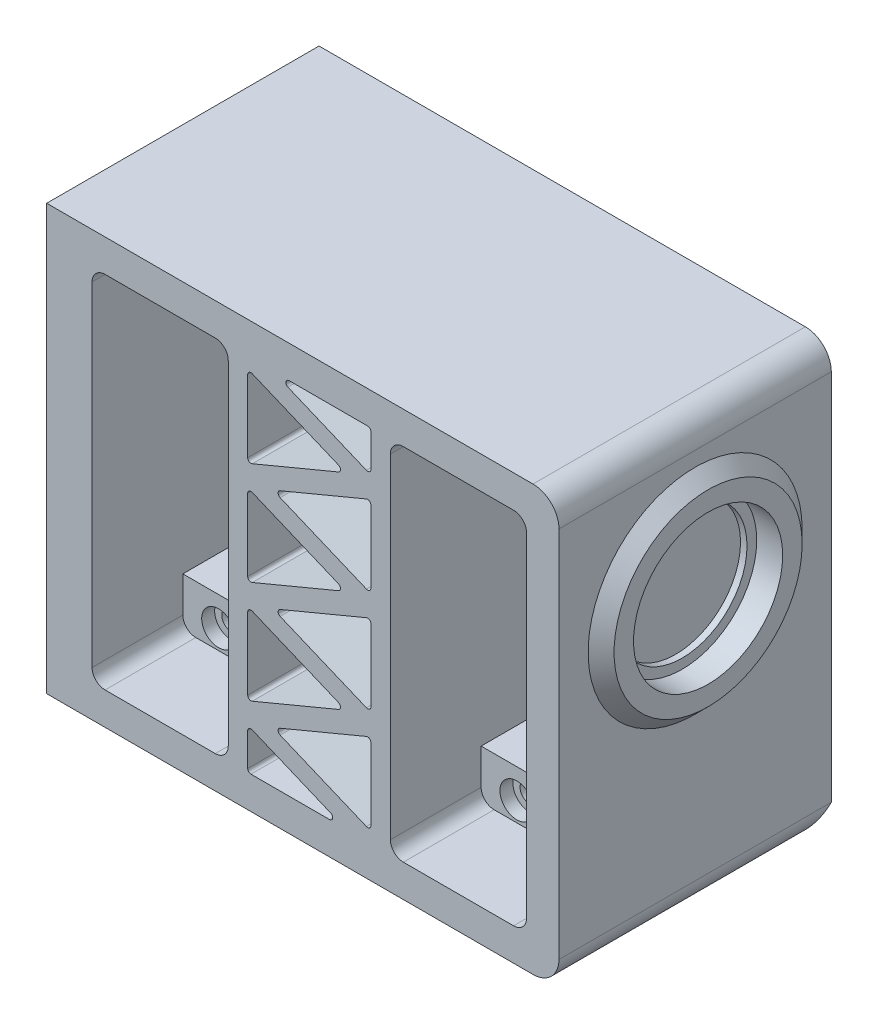
SolidWorks part; units mm, degrees
ref_plane "Front Plane" through (0, 0, 0) normal (0, 0, 1) x (1, 0, 0)
ref_plane "Top Plane" through (0, 0, 0) normal (0, 1, 0) x (1, 0, 0)
ref_plane "Right Plane" through (0, 0, 0) normal (1, 0, 0) x (0, 0, -1)
sketch "Sketch1" plane through (0, 0, 0) normal (0, 0, 1) x (1, 0, 0)
  line L0 (5, 60.5) -> (26, 60.5)
  line L1 (0, 0) -> (77, 0)
  line L2 (0, 0) -> (0, 65.5)
  line L3 (0, 65.5) -> (77, 65.5)
  line L4 (77, 0) -> (77, 65.5)
  line L5 (51, 60.5) -> (72, 60.5)
  line L6 (51, 60.5) -> (51, 5)
  line L7 (51, 5) -> (72, 5)
  line L8 (72, 60.5) -> (72, 5)
  line L9 (5, 60.5) -> (5, 5)
  line L10 (5, 5) -> (26, 5)
  line L12 (26, 60.5) -> (26, 5)
  line L13 (5, 53) -> (26, 53)
  line L14 (51, 53) -> (72, 53)
  line L15 (5, 12.5) -> (26, 12.5)
  line L16 (51, 12.5) -> (72, 12.5)
  line L17 (10.5, 57.5) -> (20.5, 57.5) construction
  line L18 (10.5, 8) -> (20.5, 8) construction
  line L19 (15.5, 57.5) -> (15.5, 8) construction
  line L20 (5, 32.75) -> (26, 32.75) construction
  line L21 (51, 32.75) -> (72, 32.75) construction
  line L22 (61.5, 57.5) -> (61.5, 8) construction
  line L23 (56.5, 57.5) -> (66.5, 57.5) construction
  line L24 (56.5, 8) -> (66.5, 8) construction
  circle A0 centre (10.5, 57.5) radius 1.5
  circle A1 centre (20.5, 57.5) radius 1.5
  circle A2 centre (10.5, 8) radius 1.5
  circle A3 centre (20.5, 8) radius 1.5
  circle A4 centre (56.5, 57.5) radius 1.5
  circle A5 centre (66.5, 57.5) radius 1.5
  circle A6 centre (66.5, 8) radius 1.5
  circle A7 centre (56.5, 8) radius 1.5
  point P33 (15.5, 32.75)
  point P34 (15.5, 32.75)
  point P41 (61.5, 32.75)
  point P42 (61.5, 32.75)
  point P53 (61.5, 8)
  point P55 (61.5, 57.5)
  dimension "D13" = 3
  dimension "D1" = 21
  dimension "D2" = 5
  dimension "D3" = 55.5
  dimension "D4" = 55.5
  dimension "D5" = 21
  dimension "D6" = 5
  dimension "D7" = 5
  dimension "D8" = 25
  dimension "D9" = 5
  dimension "D10" = 7.5
  dimension "D11" = 7.5
  dimension "D12" = 10
  dimension "D15" = 49.5
extrude "Boss-Extrude2" add sketch "Sketch1" against normal blind 28 contours L1 L4 L3 L2 L5 L8 L7 L6 L0 L12 L10 L9 | L9 L13 L12 L0 | L15 L9 L10 L12 | L16 L6 L7 L8 | L6 L14 L8 L5 | A0 | A1 | A4 | A5 | A6 | A7 | A3 | A2 region at (15.5, 56.676, 0) region at (15.5, 8.824, 0) region at (38.5, 32.75, 0) region at (61.5, 56.676, 0) region at (61.5, 8.824, 0) region at (10.5, 57.5, 0) region at (20.5, 57.5, 0) region at (56.5, 57.5, 0) region at (66.5, 57.5, 0) region at (66.5, 8, 0) region at (56.5, 8, 0)
extrude "Boss-Extrude4" add sketch "Sketch1<4>" along normal blind 14 contours L1 L4 L3 L2 L5 L8 L7 L6 L0 L12 L10 L9 region at (38.5, 32.75, 0)
sketch "Sketch1<4>" plane through (0, 0, 0) normal (0, 0, 1) x (1, 0, 0) same geometry as "Sketch1"
extrude "Cut-Extrude1" cut sketch "Sketch1<5>" against normal blind 12 contours A0 | A2 | A3 | A7 | A6 | A4 | A1 | A5 region at (10.5, 57.5, 0) region at (10.5, 8, 0) region at (20.5, 8, 0) region at (56.5, 57.5, 0) region at (66.5, 8, 0) region at (56.5, 8, 0)
sketch "Sketch1<5>" plane through (0, 0, 0) normal (0, 0, 1) x (1, 0, 0) same geometry as "Sketch1"
sketch "Sketch5" plane through (0, 0, 14) normal (0, 0, 1) x (1, 0, 0)
  line L0 (28.4223, 59.1157) -> (44.105, 52.5714)
  line L1 (26, 5) -> (51, 5)
  line L2 (26, 5) -> (26, 60.5)
  line L3 (26, 60.5) -> (51, 60.5)
  line L4 (51, 5) -> (51, 60.5)
  line L5 (26, 60.5) -> (26, 5) construction
  line L6 (51, 60.5) -> (51, 5) construction
  line L7 (5, 60.5) -> (26, 60.5) construction
  line L8 (5, 5) -> (26, 5) construction
  line L9 (29, 60.5) -> (48, 60.5)
  line L10 (48, 5) -> (48, 60.5)
  line L11 (29, 5) -> (48, 5)
  line L12 (29, 5) -> (29, 60.5)
  line L13 (29, 60.5) -> (48, 52.5714)
  line L14 (48, 52.5714) -> (29, 44.6429)
  line L15 (29, 44.6429) -> (48, 36.7143)
  line L16 (48, 36.7143) -> (29, 28.7857)
  line L17 (29, 28.7857) -> (48, 20.8571)
  line L18 (48, 20.8571) -> (29, 12.9286)
  line L19 (29, 12.9286) -> (48, 5)
  line L20 (44.105, 52.5714) -> (25.105, 44.6429)
  line L21 (25.105, 44.6429) -> (44.105, 36.7143)
  line L22 (44.105, 36.7143) -> (25.105, 28.7857)
  line L23 (25.105, 28.7857) -> (44.105, 20.8571)
  line L24 (44.105, 20.8571) -> (25.105, 12.9286)
  line L25 (25.105, 12.9286) -> (47.4223, 3.6157)
  line L26 (29.5777, 61.8843) -> (51.895, 52.5714)
  line L27 (51.895, 52.5714) -> (32.895, 44.6429)
  line L28 (32.895, 44.6429) -> (51.895, 36.7143)
  line L29 (51.895, 36.7143) -> (32.895, 28.7857)
  line L30 (32.895, 28.7857) -> (51.895, 20.8571)
  line L31 (51.895, 20.8571) -> (32.895, 12.9286)
  line L32 (32.895, 12.9286) -> (48.5777, 6.3843)
  dimension "D2" = 1.5
  dimension "D1" = 3
  dimension "D4" = 3
  dimension "D3" = 1.5
extrude "Cut-Extrude2" cut sketch "Sketch5" against normal through all contours L20 L0 L12 | L9 L26 L10 | L27 L28 L10 | L22 L21 L12 | L29 L30 L10 | L24 L23 L12 | L31 L32 L10 | L25 L12 L11 region at (34.035, 52.5714, 14) region at (42.965, 58.3989, 14) region at (34.035, 36.7143, 14) region at (42.965, 44.6429, 14) region at (42.965, 28.7857, 14) region at (34.035, 20.8571, 14) region at (42.965, 12.9286, 14) region at (34.035, 7.1011, 14)
fillet "Fillet4" radius 0.5 24 edges at (44.105, 5, -7) (29, 11.3032, -7) (29, 5, -7) (48, 6.6254, -7) (48, 19.2318, -7) (32.895, 12.9286, -7) (29, 14.5539, -7) (29, 27.1604, -7) (44.105, 20.8571, -7) (48, 22.4825, -7) (48, 35.0889, -7) (32.895, 28.7857, -7) (44.105, 36.7143, -7) (29, 30.4111, -7) (29, 43.0175, -7) (48, 38.3396, -7) (32.895, 44.6429, -7) (48, 50.9461, -7) (29, 46.2682, -7) (44.105, 52.5714, -7) (29, 58.8746, -7) (48, 54.1968, -7) (48, 60.5, -7) (32.895, 60.5, -7)
sketch "Sketch8" plane through (0, 12.5, 0) normal (0, 1, 0) x (1, 0, 0)
  line L0 (26, 28) -> (26, 0) construction
  line L1 (5, 28) -> (26, 28)
  line L2 (5, 28) -> (5, 8)
  line L3 (5, 8) -> (26, 8)
  line L4 (26, 28) -> (26, 8)
  line L5 (51, 0) -> (72, 0) construction
  line L6 (51, 28) -> (72, 28)
  line L7 (51, 28) -> (51, 8)
  line L8 (51, 8) -> (72, 8)
  line L9 (72, 28) -> (72, 8)
  line L10 (72, 28) -> (72, 0) construction
  dimension "D1" = 8
extrude "Cut-Extrude8" cut sketch "Sketch8" against normal blind 10
ref_plane "Midplane" through (0, 32.75, 0) normal (0, 1, 0) x (1, 0, 0)
ref_plane "Plane2" through (61.5, 0, 0) normal (1, 0, 0) x (0, 0, -1)
ref_plane "Plane3" through (15.5, 0, 0) normal (1, 0, 0) x (0, 0, -1)
sketch "Sketch10" plane through (61.5, 0, 0) normal (1, 0, 0) x (0, 0, -1)
  line L0 (28, 2.5) -> (8, 2.5) construction
  line L1 (8, 2.5) -> (8, 12.5) construction
  line L2 (28, 2.5) -> (8, 2.5)
  line L3 (8, 2.5) -> (8, 12.5)
  line L4 (8, 12.5) -> (18, 2.5)
  dimension "D1" = 45
extrude "Boss-Extrude5" add sketch "Sketch10" along normal blind 1.5 and the other way blind 1.5 contours L4 L3 L2 region at (61.5, 5.8333, -11.3333)
sketch "Sketch11" plane through (15.5, 0, 0) normal (1, 0, 0) x (0, 0, -1)
  line L0 (28, 2.5) -> (8, 2.5) construction
  line L1 (8, 2.5) -> (8, 12.5) construction
  line L2 (28, 2.5) -> (8, 2.5)
  line L3 (8, 2.5) -> (8, 12.5)
  line L4 (8, 12.5) -> (18, 2.5)
  dimension "D1" = 45
extrude "Boss-Extrude6" add sketch "Sketch11" along normal blind 1.5 and the other way blind 1.5 contours L4 L3 L2 region at (15.5, 5.8333, -11.3333)
mirror "Mirror2" about plane through (0, 32.75, 0) normal (0, 1, 0) of "Boss-Extrude6", "Boss-Extrude5", "Cut-Extrude8"
sketch "Sketch13" plane through (0, 0, 0) normal (-1, 0, 0) x (0, 0, 1)
  line L4 (-28, 0) -> (14, 0)
  line L5 (14, 0) -> (14, 65.5)
  line L6 (14, 65.5) -> (-28, 65.5)
  line L7 (-28, 65.5) -> (-28, 0)
  line L8 (-28, 0) -> (14, 0)
  line L9 (14, 0) -> (14, 65.5)
  line L10 (14, 65.5) -> (-28, 65.5)
  line L11 (-28, 65.5) -> (-28, 0)
  dimension "D1" = 0
extrude "Boss-Extrude7" add sketch "Sketch13" along normal blind 2
fillet "Fillet3" radius 2 16 edges at (51, 60.5, 7) (72, 5, 7) (72, 60.5, 7) (51, 5, 7) (5, 5, 7) (26, 5, 7) (26, 60.5, 7) (5, 60.5, 7) (72, 63, -18) (72, 2.5, -18) (51, 2.5, -18) (51, 63, -18) (26, 63, -18) (26, 2.5, -18) (5, 63, -18) (5, 2.5, -18)
sketch "Sketch14" plane through (-2, 0, 0) normal (-1, 0, 0) x (0, 0, 1)
  line L8 (-24, 61.5) -> (-24, 4)
  line L9 (-24, 4) -> (10, 4)
  line L10 (10, 4) -> (10, 61.5)
  line L11 (10, 61.5) -> (-24, 61.5)
  line L12 (-24, 61.5) -> (-24, 4) construction
  line L13 (-24, 4) -> (10, 4) construction
  line L14 (10, 4) -> (10, 61.5) construction
  line L15 (10, 61.5) -> (-24, 61.5) construction
  circle A0 centre (-24, 61.5) radius 1.25
  circle A1 centre (10, 61.5) radius 1.25
  circle A2 centre (10, 4) radius 1.25
  circle A3 centre (-24, 4) radius 1.25
  dimension "D2" = 2.5
  dimension "D1" = 4
extrude "Cut-Extrude9" cut sketch "Sketch14" against normal blind 7
fillet "Fillet7" radius 4 2 edges at (77, 65.5, -7) (77, 0, -7)
sketch "Sketch15" plane through (77, 0, 0) normal (1, 0, 0) x (0, 0, -1)
  line L0 (-14, 32.75) -> (28, 32.75) construction
  line L1 (-14, 4) -> (-14, 61.5) construction
  line L2 (28, 4) -> (28, 61.5) construction
  line L3 (-14, 42.75) -> (28, 42.75) construction
  circle A0 centre (7, 42.75) radius 13.5
  dimension "D2" = 27
  dimension "D1" = 10
extrude "Boss-Extrude8" add sketch "Sketch15" along normal blind 2
sketch "Sketch16" plane through (79, 0, 0) normal (1, 0, 0) x (0, 0, -1)
  circle A0 centre (7, 42.75) radius 11.5
  dimension "D1" = 23
extrude "Cut-Extrude10" cut sketch "Sketch16" against normal blind 4
chamfer "Chamfer1" distance 3 angle 45 1 edges at (77, 42.75, -20.5)
sketch "Sketch17" plane through (75, 0, 0) normal (1, 0, 0) x (0, 0, -1)
  circle A0 centre (7, 42.75) radius 10
  dimension "D1" = 20
extrude "Cut-Extrude11" cut sketch "Sketch17" against normal blind 1
sketch "Sketch18" plane through (0, 0, 0) normal (0, 0, 1) x (1, 0, 0)
  circle A0 centre (10.5, 57.5) radius 2.6
  circle A1 centre (20.5, 57.5) radius 2.6
  circle A2 centre (56.5, 57.5) radius 2.6
  circle A3 centre (66.5, 57.5) radius 2.6
  circle A4 centre (66.5, 8) radius 2.6
  circle A5 centre (56.5, 8) radius 2.6
  circle A6 centre (20.5, 8) radius 2.6
  circle A7 centre (10.5, 8) radius 2.6
  dimension "D1" = 5.2
extrude "Cut-Extrude12" cut sketch "Sketch18" against normal blind 2
sketch "Sketch19" plane through (-2, 0, 0) normal (-1, 0, 0) x (0, 0, 1)
  line L0 (-28, 4) -> (-24, 0)
  line L1 (-28, 65.5) -> (-28, 0) construction
  line L2 (-28, 0) -> (14, 0) construction
  line L3 (-28, 4) -> (-28, 0)
  line L4 (-28, 0) -> (-24, 0)
  dimension "D1" = 4
extrude "Cut-Extrude13" cut sketch "Sketch19" against normal through all
